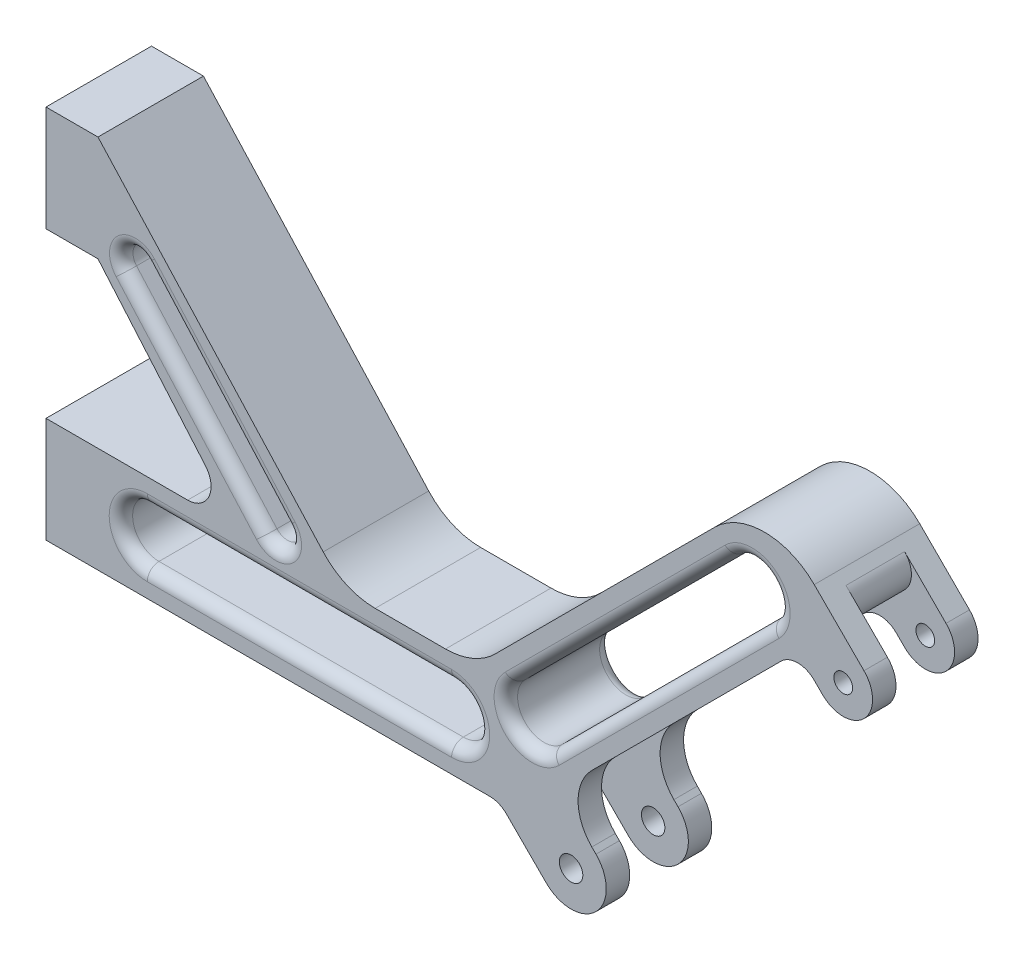
SolidWorks part; units mm, degrees
material "6061 Alloy"
ref_plane "Front Plane" through (0, 0, 0) normal (0, 0, 1) x (1, 0, 0)
ref_plane "Top Plane" through (0, 0, 0) normal (0, 1, 0) x (1, 0, 0)
ref_plane "Right Plane" through (0, 0, 0) normal (1, 0, 0) x (0, 0, -1)
sketch "Sketch1" plane through (0, 0, 0) normal (1, 0, 0) x (0, 0, -1)
  line L1 (-20, 20) -> (20, 20)
  line L2 (-20, 20) -> (-20, -20)
  line L3 (-20, -20) -> (20, -20)
  line L4 (20, 20) -> (20, -20) construction
  line L5 (-20, 20) -> (20, -20) construction
  line L6 (-20, -20) -> (20, 20) construction
  line L7 (-22.5, 22.5) -> (22.5, 22.5)
  line L8 (-22.5, 22.5) -> (-22.5, -22.5)
  line L9 (-22.5, -22.5) -> (22.5, -22.5)
  line L10 (22.5, 22.5) -> (22.5, -22.5)
  line L11 (-22.5, 22.5) -> (22.5, -22.5) construction
  line L12 (-22.5, -22.5) -> (22.5, 22.5) construction
  point P0 (0, 0)
  point P6 (0, 0)
  dimension "D1" = 40
  dimension "D2" = 40
  dimension "D3" = 45
  dimension "D4" = 45
sketch "Sketch2" plane through (0, 0, 0) normal (0, 0, 1) x (1, 0, 0)
  line L0 (0, 0) -> (170, 0)
  line L1 (300.2297, 0) -> (300.2297, 130.2297) construction
  line L2 (300.2297, 35.5495) -> (173.2297, 35.5495) construction
  line L3 (300.2297, 130.2297) -> (170, 0)
  line L4 (170, 0) -> (300.2297, 0) construction
  line L5 (300.2297, 130.2297) -> (347.9594, 82.5)
  line L6 (347.9594, 82.5) -> (326.7462, 61.2868)
  line L7 (326.7462, 61.2868) -> (279.0165, 109.0165)
  line L8 (337.3528, 71.8934) -> (324.9741, 84.2721) construction
  line L9 (326.7462, 82.5) -> (326.7462, 0) construction
  line L10 (300.2297, 0) -> (326.7462, 0)
  line L11 (82.5, 22.5) -> (82.5, 37.8458) construction
  line L12 (0, 22.5) -> (92.0876, 22.5)
  line L13 (0, 22.5) -> (0, -22.5) construction
  line L14 (0, 22.5) -> (0, -22.5) construction
  line L15 (82.5, 22.5) -> (0, 105)
  line L16 (0, 22.5) -> (0, 105) construction
  arc A0 (34.4369, 70.5631) -> (25.2297, 0) centre (300.2297, 0) ccw construction
  circle A1 centre (326.7462, 82.5) radius 5.9071
  dimension "D2" = 550
  dimension "D7" = 15
  dimension "D4" = 82.5
  dimension "D1" = 170
  dimension "D3" = 135
  dimension "D5" = 30
  dimension "D6" = 67.5
  dimension "D8" = 82.5
  dimension "D9" = 45
sweep "Sweep1" add profiles "Sketch1" path "Sketch2"
sketch "Sketch5" plane through (0, 0, 22.5) normal (0, 0, 1) x (1, 0, 0)
  line L0 (170, 0) -> (212.4264, -42.4264) construction
  line L1 (179.3198, -22.5) -> (160.6802, 22.5) construction
  line L2 (179.3198, -22.5) -> (0, -22.5) construction
  line L3 (201.8198, -53.033) -> (159.3934, -10.6066)
  line L4 (159.3934, -10.6066) -> (180.6066, 10.6066)
  line L5 (201.8198, -53.033) -> (223.033, -31.8198)
  line L6 (223.033, -31.8198) -> (180.6066, 10.6066)
  line L7 (170, 0) -> (0, 0) construction
  line L8 (170, 0) -> (282.552, 112.552) construction
  line L9 (284.3198, 146.1396) -> (316.1396, 114.3198) construction
  line L10 (300.2297, 130.2297) -> (335.585, 94.8744)
  line L11 (335.585, 94.8744) -> (317.9074, 77.1967)
  line L12 (317.9074, 77.1967) -> (282.552, 112.552)
  line L13 (326.7462, 86.0355) -> (307.4546, 105.3272) construction
  line L14 (300.2297, 130.2297) -> (282.552, 112.552)
  circle A0 centre (201.8198, -31.8198) radius 5
  circle A1 centre (317.9074, 94.8744) radius 4
  point P9 (212.4264, -42.4264)
  point P14 (170, 0)
  dimension "D4" = 10
  dimension "D5" = 15
  dimension "D8" = 8
  dimension "D9" = 12.5
  dimension "D1" = 135
  dimension "D2" = 60
  dimension "D3" = 30
  dimension "D6" = 50
  dimension "D7" = 25
  dimension "D10" = 159.1726
extrude "Boss-Extrude2" add sketch "Sketch5" against normal blind 10
fillet "Fillet2" radius 15 2 edges at (201.8198, -53.033, 17.5) (223.033, -31.8198, 17.5)
mirror "Mirror1" about plane through (0, 0, 0) normal (0, 0, 1) of "Boss-Extrude2", "Fillet2"
sketch "Sketch6" plane through (0, 22.5, 0) normal (0, 1, 0) x (1, 0, 0)
  line L0 (0, 0) -> (170, 0) construction
  line L1 (60, 22.5) -> (105, 22.5)
  line L2 (60, 22.5) -> (60, -22.5)
  line L3 (60, -22.5) -> (105, -22.5)
  line L4 (105, 22.5) -> (105, -22.5)
  line L5 (60, 22.5) -> (105, -22.5) construction
  line L6 (60, -22.5) -> (105, 22.5) construction
  line L7 (160.6802, -22.5) -> (0, -22.5) construction
  line L8 (0, 22.5) -> (0, -22.5) construction
  point P0 (82.5, 0)
  dimension "D1" = 60
sketch "Sketch7" plane through (0, 0, 0) normal (-1, 0, 0) x (0, 0, 1)
  line L0 (0, 130.2297) -> (0, 82.5) construction
  line L1 (-22.5, 137.5) -> (22.5, 137.5)
  line L2 (-22.5, 137.5) -> (-22.5, 92.5)
  line L3 (-22.5, 92.5) -> (22.5, 92.5)
  line L4 (22.5, 137.5) -> (22.5, 92.5)
  line L5 (-22.5, 137.5) -> (22.5, 92.5) construction
  line L6 (-22.5, 92.5) -> (22.5, 137.5) construction
  line L7 (22.5, 22.5) -> (-22.5, 22.5) construction
  point P0 (0, 115)
  point P16 (22.5, -22.5)
  dimension "D1" = 45
  dimension "D2" = 70
loft "Loft1" add profiles "Sketch6", "Sketch7" connector at (105, 22.5, -22.5) connector at (0, 137.5, -22.5)
fillet "Fillet3" radius 10 5 edges at (298.4619, 96.6421, 17.5) (298.4619, 96.6421, -17.5) (171.2868, -22.5, -17.5) (171.2868, -22.5, 17.5) tangent propagation no
fillet "Fillet4" radius 30 1 edges at (284.3198, 146.1396, 0)
fillet "Fillet5" radius 30 1 edges
sketch "Sketch8" plane through (0, 0, 22.5) normal (0, 0, 1) x (1, 0, 0)
  line L0 (21.0386, 0) -> (150.8392, 0) construction
  line L1 (0, 0) -> (170, 0) construction
  line L2 (21.0386, 11.25) -> (150.8392, 11.25)
  line L3 (21.0386, -11.25) -> (150.8392, -11.25)
  line L4 (185.2441, 15.2441) -> (279.0165, 109.0165) construction
  line L5 (300.2297, 130.2297) -> (170, 0) construction
  line L6 (177.2891, 23.1991) -> (271.0616, 116.9715)
  line L7 (193.1991, 7.2891) -> (286.9715, 101.0616)
  line L8 (0, 115) -> (82.5, 22.5) construction
  line L9 (0, 92.5) -> (0, 137.5) construction
  line L10 (15.9385, 97.1295) -> (82.5, 22.5) construction
  line L11 (20.4163, 101.1232) -> (86.9778, 26.4937)
  line L12 (11.4607, 93.1359) -> (78.0222, 18.5063)
  line L13 (82.5, 22.5) -> (75.8439, 29.963)
  arc A0 (21.0386, 11.25) -> (21.0386, -11.25) centre (21.0386, 0) ccw
  arc A1 (150.8392, -11.25) -> (150.8392, 11.25) centre (150.8392, 0) ccw
  arc A2 (177.2891, 23.1991) -> (193.1991, 7.2891) centre (185.2441, 15.2441) ccw
  arc A3 (286.9715, 101.0616) -> (271.0616, 116.9715) centre (279.0165, 109.0165) ccw
  arc A4 (20.4163, 101.1232) -> (11.4607, 93.1359) centre (15.9385, 97.1295) ccw
  arc A5 (78.0222, 18.5063) -> (86.9778, 26.4937) centre (82.5, 22.5) ccw
  arc A6 (71.3661, 25.9693) -> (80.3216, 33.9566) centre (75.8439, 29.963) ccw
  point P4 (85.9389, 0)
  point P9 (232.1303, 62.1303)
  point P25 (49.2193, 59.8148)
  dimension "D1" = 11.25
  dimension "D2" = 11.25
  dimension "D3" = 6
  dimension "D4" = 100
  dimension "D5" = 10
extrude "Cut-Extrude1" cut sketch "Sketch8" against normal through all contours L7 A3 L6 A2 | L12 A6 L11 A4 | L3 A1 L2 A0 region at (232.1303, 62.1303, 22.5) region at (45.8912, 63.5462, 22.5)
fillet "Fillet6" radius 5 20 edges at (41.4134, 59.5526, 22.5) (11.9448, 101.6073, 22.5) (50.369, 67.5399, 22.5) (240.0853, 54.1754, 22.5) (177.2891, 7.2891, 22.5) (224.1754, 70.0853, 22.5) (162.0892, 0, 22.5) (85.9389, -11.25, 22.5) (9.7886, 0, 22.5) (9.7886, 0, -22.5) (85.9389, 11.25, -22.5) (162.0892, 0, -22.5) (177.2891, 7.2891, -22.5) (224.1754, 70.0853, -22.5) (286.9715, 116.9715, -22.5) (286.9715, 116.9715, 22.5) (85.9389, 11.25, 22.5) (85.9389, -11.25, -22.5) (240.0853, 54.1754, -22.5) (79.8375, 25.4852, 22.5)
fillet "Fillet7" radius 20 2 edges at (196.5165, -5.3033, 17.5) (196.5165, -5.3033, -17.5)
fillet "Fillet8" radius 25 1 edges at (179.3198, -22.5, 0)
fillet "Fillet10" radius 5 4 edges at (11.9448, 101.6073, -22.5) (41.4134, 59.5526, -22.5) (79.8375, 25.4852, -22.5) (50.369, 67.5399, -22.5)
fillet "Fillet11" radius 10 1 edges at (316.1396, 114.3198, 0)
fillet "Fillet12" radius 30 1 edges at (160.6802, 22.5, 0)
sketch "Sketch9" plane through (0, 0, 0) normal (-1, 0, 0) x (0, 0, 1)
  line L1 (-22.5, 22.5) -> (22.5, 22.5)
  line L2 (-22.5, 22.5) -> (-22.5, -22.5)
  line L3 (-22.5, -22.5) -> (22.5, -22.5)
  line L4 (22.5, 22.5) -> (22.5, -22.5)
  line L5 (-22.5, 137.5) -> (22.5, 137.5)
  line L6 (-22.5, 137.5) -> (-22.5, 92.5)
  line L7 (-22.5, 92.5) -> (22.5, 92.5)
  line L8 (22.5, 137.5) -> (22.5, 92.5)
extrude "Boss-Extrude3" add sketch "Sketch9" along normal blind 22.16
fillet "Fillet13" radius 12.5 4 edges at (335.585, 94.8744, -17.5) (317.9074, 77.1967, -17.5) (317.9074, 77.1967, 17.5) (335.585, 94.8744, 17.5)
